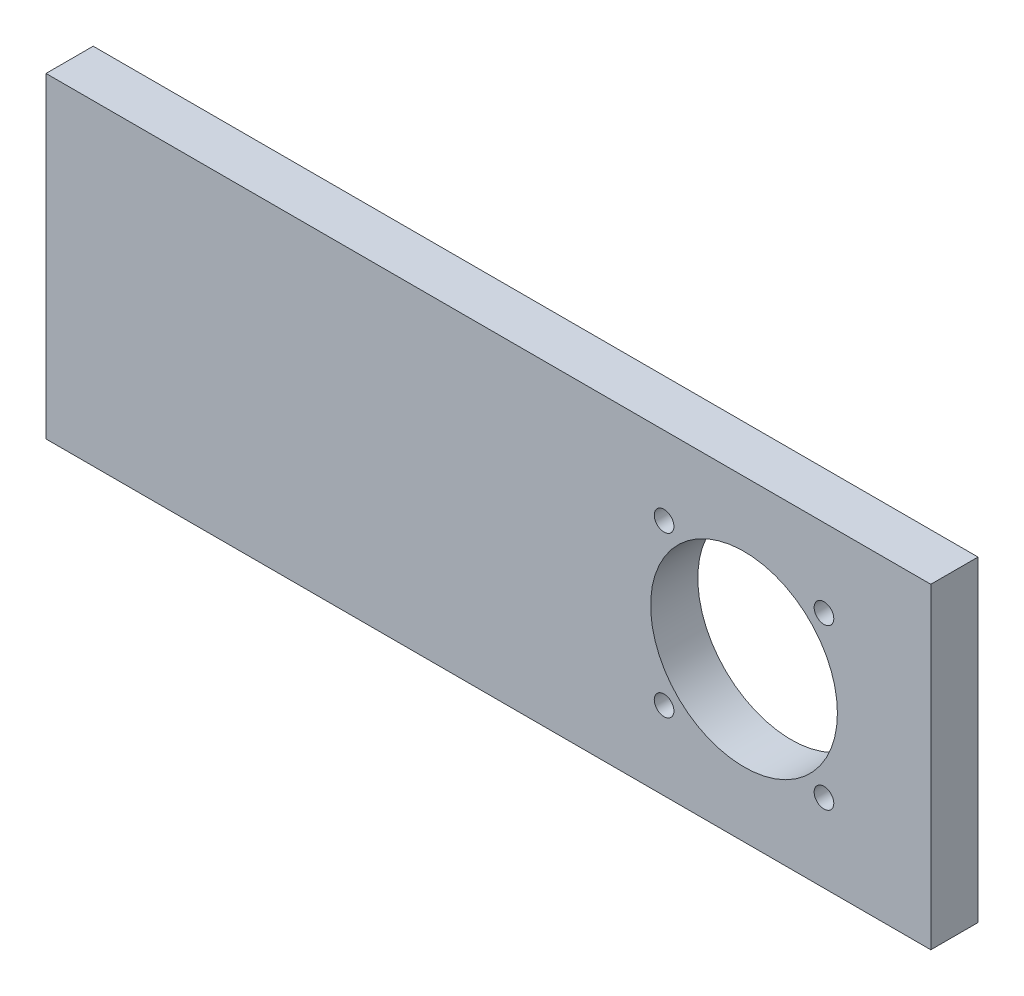
SolidWorks part; units mm, degrees
ref_plane "前视基准面" through (0, 0, 0) normal (0, 0, 1) x (1, 0, 0)
ref_plane "上视基准面" through (0, 0, 0) normal (0, 1, 0) x (1, 0, 0)
ref_plane "右视基准面" through (0, 0, 0) normal (1, 0, 0) x (0, 0, -1)
other "Configuration Table"
sketch "草图1" plane through (0, 0, 0) normal (0, 0, 1) x (1, 0, 0)
  line L0 (-225, 0) -> (225, 0) construction
  line L1 (-225, 80.5) -> (225, 80.5)
  line L2 (-225, 80.5) -> (-225, -80.5)
  line L3 (-225, -80.5) -> (225, -80.5)
  line L4 (225, 80.5) -> (225, -80.5)
  line L5 (-225, 80.5) -> (225, -80.5) construction
  line L6 (-225, -80.5) -> (225, 80.5) construction
  line L7 (0, 0) -> (0, 80.5) construction
  line L8 (130, 0) -> (130, 57.5) construction
  circle A0 centre (130, 0) radius 47.5
  circle A1 centre (130, 0) radius 57.5 construction
  circle A3 centre (170.6586, 40.6586) radius 5
  circle A4 centre (170.6586, -40.6586) radius 5
  circle A5 centre (89.3414, -40.6586) radius 5
  circle A6 centre (89.3414, 40.6586) radius 5
  point P0 (0, 0)
  point P25 (130, 0)
  dimension "D3" = 95
  dimension "D5" = 115
  dimension "D6" = 10
  dimension "D1" = 450
  dimension "D2" = 161
  dimension "D4" = 95
  dimension "D7" = 45
  dimension "D8" = 4
extrude "凸台-拉伸1" add sketch "草图1" along normal blind 24 contours L4 L3 L2 L1 | A0
extrude "切除-拉伸1" cut sketch "草图1<3>" against normal blind 18 from surface contours A6 | A3 | A4 | A5 region at (89.3414, 40.6586, 0) starting at face at (0, 0, 24)
sketch "草图1<3>" plane through (0, 0, 0) normal (0, 0, 1) x (1, 0, 0) same geometry as "草图1"
